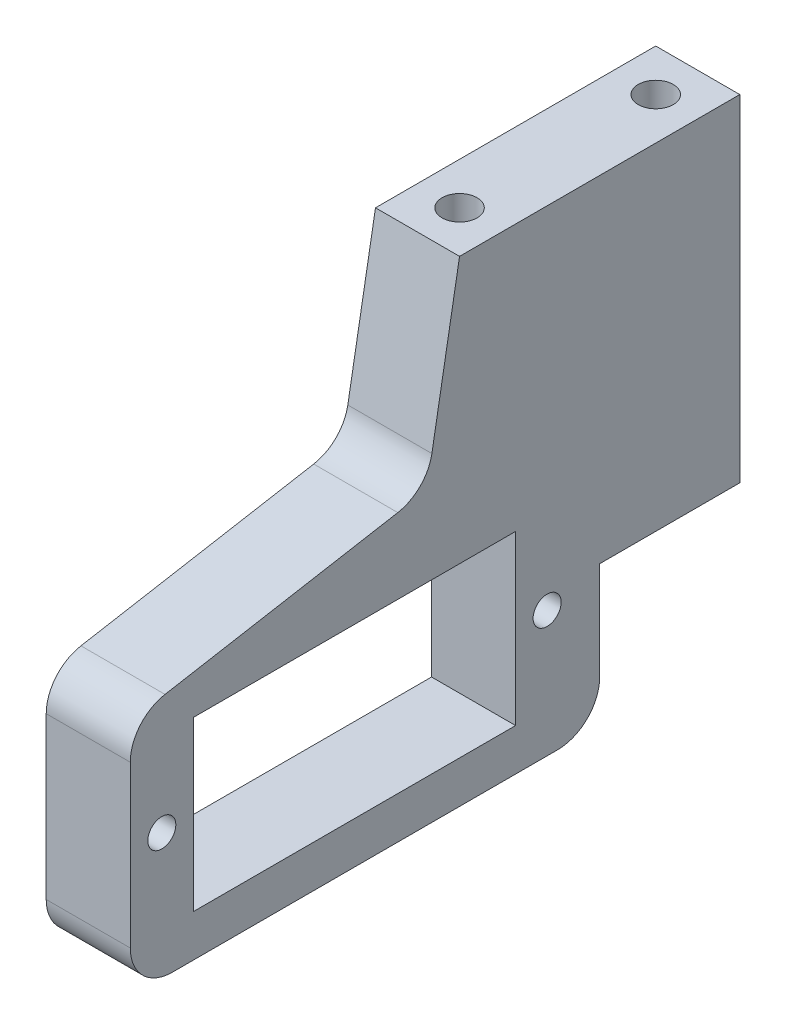
SolidWorks part; units mm, degrees
ref_plane "Front Plane" through (0, 0, 0) normal (0, 0, 1) x (1, 0, 0)
ref_plane "Top Plane" through (0, 0, 0) normal (0, 1, 0) x (1, 0, 0)
ref_plane "Right Plane" through (0, 0, 0) normal (1, 0, 0) x (0, 0, -1)
sketch "Sketch2" plane through (0, 0, 0) normal (1, 0, 0) x (0, 0, -1)
  line L0 (-16, -31) -> (-39, -31)
  line L1 (-20, 0) -> (-22.3397, -13.2689)
  line L2 (-22.3397, -13.2689) -> (-43.5, -17)
  line L8 (0, -34) -> (0, 0)
  line L9 (-43.5, -34) -> (0, -34)
  line L10 (-16, -19) -> (-16, -31)
  line L11 (-39, -19) -> (-16, -19)
  line L12 (-39, -31) -> (-39, -19)
  line L14 (-43.5, -17) -> (-43.5, -34)
  line L16 (0, 0) -> (-20, 0)
  circle A2 centre (-41.25, -25) radius 1
  circle A3 centre (-13.75, -25) radius 1
  dimension "D8" = 20
  dimension "D9" = 6
  dimension "D11" = 2
  dimension "D1" = 19
  dimension "D2" = 39
  dimension "D3" = 3
  dimension "D4" = 2.25
  dimension "D5" = 2.25
  dimension "D6" = 4.5
  dimension "D7" = 12
  dimension "D10" = 23
  dimension "D12" = 100
  dimension "D13" = 100
  dimension "D14" = 2
extrude "Boss-Extrude1" add sketch "Sketch2" along normal blind 6
sketch "Sketch3" plane through (0, 0, 0) normal (-1, 0, 0) x (0, 0, 1)
  line L1 (0, -34) -> (10, -34)
  line L2 (0, -34) -> (0, -24)
  line L3 (0, -24) -> (10, -24)
  line L4 (10, -34) -> (10, -24)
  dimension "D1" = 10
  dimension "D2" = 10
extrude "Cut-Extrude1" cut sketch "Sketch3" against normal up to next
fillet "Fillet1" radius 3 4 edges at (3, -13.2689, 22.3397) (3, -34, 10) (3, -34, 43.5) (3, -17, 43.5)
hole_wizard "Tap Drill for M3x0.5 Tap1" positions "3DSketch1" profile "Sketch4" hole size "M3x0.5" standard "ANSI Metric"
sketch3d "3DSketch1"
  line L0 (6, -24, 0) -> (0, -24, 0) construction
  line L1 (6, -24, 10) -> (6, -24, 0) construction
  line L2 (0, 0, 0) -> (0, 0, 20) construction
  line L3 (6, 0, 0) -> (0, 0, 0) construction
  line L4 (6, 0, 20) -> (0, 0, 20) construction
  point P0 (3, 0, 3)
  point P2 (3, 0, 17)
  point P4 (3, -24, 5)
  dimension "D1" = 5
  dimension "D2" = 3
  dimension "D3" = 3
  dimension "D4" = 3
  dimension "D5" = 3
  dimension "D6" = 3
sketch "Sketch4" plane through (3, 0, 3) normal (1, 0, 0) x (0, 0, 1)
  line L0 (0, 0) -> (0, 10.7511)
  line L1 (0, 10.7511) -> (1.25, 10)
  line L2 (1.25, 10) -> (1.25, 0)
  line L5 (1.25, 0) -> (0, 0)
  line L10 (0, 10.7511) -> (-1.25, 10) construction
  line L11 (0, -6.35) -> (0, 107.95) construction
  dimension "Hole Dia." = 2.5
  dimension "Hole Depth" = 10
  dimension "Drill Angle" = 118
